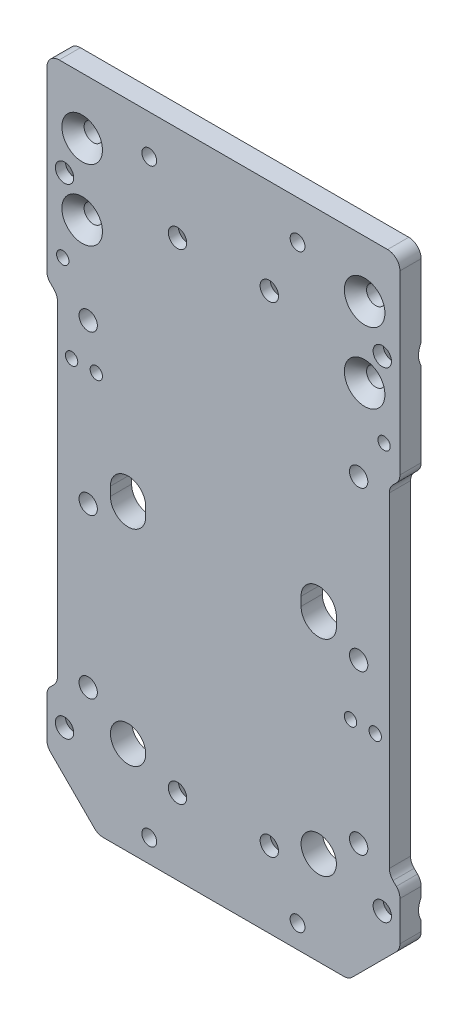
SolidWorks part; units mm, degrees
material "Acrylic (Medium-high impact)"
ref_plane "Front Plane" through (0, 0, 0) normal (0, 0, 1) x (1, 0, 0)
ref_plane "Top Plane" through (0, 0, 0) normal (0, 1, 0) x (1, 0, 0)
ref_plane "Right Plane" through (0, 0, 0) normal (1, 0, 0) x (0, 0, -1)
sketch "Sketch1" plane through (0, 0, 0) normal (0, 0, 1) x (1, 0, 0)
  line L0 (-50, 0) -> (-35.5, -14.5)
  line L1 (-50, 0) -> (50, 0)
  line L2 (-50, 0) -> (-50, 170)
  line L3 (-50, 170) -> (50, 170)
  line L4 (50, 0) -> (50, 170)
  line L5 (-35.5, -14.5) -> (35.5, -14.5)
  line L6 (35.5, -14.5) -> (50, 0)
  line L7 (0, 0) -> (0, 178.5984) construction
  point P4 (0, 0)
  point P8 (0, -14.5)
  dimension "D1" = 100
  dimension "D2" = 170
  dimension "D3" = 14.5
  dimension "D4" = 71
  dimension "D5" = 184.5
extrude "Body" add sketch "Sketch1" along normal mid plane 6 contours L1 L4 L3 L2 | L5 L6 L1 L0 | L1 L7 L3 L2 region at (0, -6.8402, 0) region at (-25, 85, 0) region at (25, 85, 0)
sketch "Sketch6" plane through (0, 0, 3) normal (0, 0, 1) x (1, 0, 0)
  line L0 (-50, 115) -> (-47, 112)
  line L1 (0, 0) -> (0, 25.1631) construction
  line L2 (-47, 112) -> (-47, 17)
  line L3 (-47, 17) -> (-50, 14)
  line L4 (50, 115) -> (47, 112)
  line L5 (-35.5, -14.5) -> (35.5, -14.5) construction
  line L6 (47, 112) -> (47, 17)
  line L7 (47, 17) -> (50, 14)
  line L8 (-50, 115) -> (-50, 14)
  line L9 (50, 115) -> (50, 14)
  line L12 (-50, 0) -> (-50, 170) construction
  line L13 (50, 0) -> (50, 170) construction
  dimension "D1" = 94
  dimension "D2" = 28.5
  dimension "D3" = 45
  dimension "D4" = 129.5
extrude "ReduceSomeWidth" cut sketch "Sketch6" against normal through all
sketch "screwHeadHoleCarriageY" plane through (0, 0, -3) normal (0, 0, -1) x (-1, 0, 0)
  line L0 (0, 0) -> (0, 34.2129) construction
  line L1 (35.5, -14.5) -> (-35.5, -14.5) construction
  line L2 (-27, 70.2) -> (-27, 72.7) construction
  line L3 (-32, 70.2) -> (-32, 72.7)
  line L4 (-22, 70.2) -> (-22, 72.7)
  line L5 (27, 70.2) -> (27, 72.7) construction
  line L6 (22, 70.2) -> (22, 72.7)
  line L7 (32, 70.2) -> (32, 72.7)
  circle A0 centre (-27, 12) radius 5
  circle A1 centre (27, 12) radius 5
  arc A6 (-32, 70.2) -> (-22, 70.2) centre (-27, 70.2) ccw
  arc A7 (-22, 72.7) -> (-32, 72.7) centre (-27, 72.7) ccw
  arc A8 (22, 70.2) -> (32, 70.2) centre (27, 70.2) ccw
  arc A9 (32, 72.7) -> (22, 72.7) centre (27, 72.7) ccw
  point P18 (-27, 71.45)
  point P28 (27, 71.45)
  dimension "D3" = 10
  dimension "D5" = 12.5
  dimension "D1" = 54
  dimension "D2" = 26.5
  dimension "D4" = 84.7
extrude "CutForOtherScrewsHeads" cut sketch "screwHeadHoleCarriageY" against normal through all
fillet "EndMillMinimumRadius" radius 3.5 14 edges at (-50, 170, 0) (50, 170, 0) (47, 112, 0) (47, 17, 0) (-47, 17, 0) (-47, 112, 0) (-50, 14, 0) (-50, 0, 0) (-35.5, -14.5, 0) (50, 14, 0) (50, 0, 0) (35.5, -14.5, 0) (-50, 115, 0) (50, 115, 0)
hole_wizard "Ø3.5 (3.5) CableTieHoles" positions "Sketch9" profile "Sketch10" hole size "Ø3.5" standard "ANSI Metric" end condition through all
sketch "Sketch9" plane through (0, 0, -3) normal (0, 0, -1) x (-1, 0, 0)
  line L0 (-50, 116.4497) -> (-50, 166.5) construction
  line L1 (50, 116.4497) -> (50, 166.5) construction
  line L2 (34.0503, -14.5) -> (-34.0503, -14.5) construction
  point P0 (-45.5, 122)
  point P2 (45.5, 122)
  dimension "D1" = 4.5
  dimension "D2" = 4.5
  dimension "D3" = 136.5
sketch "Sketch10" plane through (45.5, 122, -3) normal (1, 0, 0) x (0, 1, 0)
  line L0 (0, 0) -> (0, 6)
  line L1 (0, 6) -> (1.75, 6)
  line L2 (1.75, 6) -> (1.75, 0)
  line L5 (1.75, 0) -> (0, 0)
  line L11 (0, -6.35) -> (0, 107.95) construction
  dimension "Thru Hole Dia." = 3.5
  dimension "Thru Hole Depth" = 6
hole_wizard "Ø4.2 (4.2) KP8 Holes1" positions "Sketch11" profile "Sketch12" hole size "Ø4.2" standard "ANSI Metric" end condition through all
sketch "Sketch11" plane through (0, 0, -3) normal (0, 0, -1) x (-1, 0, 0)
  line L0 (34.0503, -14.5) -> (-34.0503, -14.5) construction
  line L2 (0, 0) -> (0, 41.1682) construction
  point P0 (-21, 159)
  point P2 (21, 159)
  dimension "D1" = 42
  dimension "D2" = 173.5
sketch "Sketch12" plane through (21, 159, -3) normal (1, 0, 0) x (0, 1, 0)
  line L0 (0, 0) -> (0, 6)
  line L1 (0, 6) -> (2.1, 6)
  line L2 (2.1, 6) -> (2.1, 0)
  line L5 (2.1, 0) -> (0, 0)
  line L11 (0, -6.35) -> (0, 107.95) construction
  dimension "Thru Hole Dia." = 4.2
  dimension "Thru Hole Depth" = 6
hole_wizard "Ø4.2 (4.2) KP8 Holes2" positions "Sketch13" profile "Sketch14" hole size "Ø4.2" standard "ANSI Metric" end condition through all
sketch "Sketch13" plane through (0, 0, -3) normal (0, 0, -1) x (-1, 0, 0)
  line L0 (34.0503, -14.5) -> (-34.0503, -14.5) construction
  line L1 (0, 0) -> (0, 17.4832) construction
  point P0 (-21, -8)
  point P2 (21, -8)
  dimension "D1" = 42
  dimension "D2" = 6.5
sketch "Sketch14" plane through (21, -8, -3) normal (1, 0, 0) x (0, 1, 0)
  line L0 (0, 0) -> (0, 6)
  line L1 (0, 6) -> (2.1, 6)
  line L2 (2.1, 6) -> (2.1, 2.7)
  line L3 (2.1, 2.7) -> (4.8, 0)
  line L5 (4.8, 0) -> (0, 0)
  line L6 (-2.1, 2.7) -> (-4.8, 0) construction
  line L11 (0, -6.35) -> (0, 107.95) construction
  dimension "Thru Hole Dia." = 4.2
  dimension "Thru Hole Depth" = 6
  dimension "Near C'Sink Dia." = 9.6
  dimension "Near C'Sink Angle" = 90
hole_wizard "Ø5.2 (5.2) MountAngleCornerHoles" positions "Sketch15" profile "Sketch16" hole size "Ø5.2" standard "ANSI Metric" end condition through all
sketch "Sketch15" plane through (0, 0, -3) normal (0, 0, -1) x (-1, 0, 0)
  line L0 (0, 0) -> (0, 24.2214) construction
  line L2 (46.5, 170) -> (-46.5, 170) construction
  point P0 (-40, 154)
  point P2 (-40, 134)
  point P4 (40, 154)
  point P6 (40, 134)
  dimension "D1" = 80
  dimension "D2" = 20
  dimension "D3" = 16
sketch "Sketch16" plane through (40, 154, -3) normal (1, 0, 0) x (0, 1, 0)
  line L0 (0, 0) -> (0, 6)
  line L1 (0, 6) -> (5.75, 6)
  line L2 (2.6, 2.85) -> (2.6, 0)
  line L5 (2.6, 0) -> (0, 0)
  line L7 (5.75, 6) -> (2.6, 2.85)
  line L8 (-5.75, 6) -> (-2.6, 2.85) construction
  line L11 (0, -6.35) -> (0, 107.95) construction
  dimension "Thru Hole Dia." = 5.2
  dimension "Thru Hole Depth" = 6
  dimension "Far C'Sink Dia." = 11.5
  dimension "Far C'Sink Angle" = 90
hole_wizard "Ø5.2 (5.2) SK8 Mount Holes" positions "Sketch17" profile "Sketch20" hole size "Ø5.2" standard "ANSI Metric" end condition through all
sketch "Sketch17" plane through (0, 0, -3) normal (0, 0, -1) x (-1, 0, 0)
  line L0 (0, 0) -> (0, 35.1955) construction
  line L1 (34.0503, -14.5) -> (-34.0503, -14.5) construction
  point P0 (-45, 143.1)
  point P2 (-13, 143.1)
  point P4 (13, 143.1)
  point P6 (45, 143.1)
  point P8 (-45, 7)
  point P10 (-13, 7)
  point P12 (13, 7)
  point P14 (45, 7)
  point P23 (0, 0)
  point P24 (-9.1751, 131.7209)
  point P25 (0, 0)
  point P26 (0, 0)
  point P27 (0, 0)
  point P28 (0, 0)
  point P29 (0, 0)
  dimension "D1" = 32
  dimension "D2" = 26
  dimension "D3" = 32
  dimension "D4" = 21.5
  dimension "D5" = 157.6
sketch "Sketch20" plane through (45, 143.1, -3) normal (1, 0, 0) x (0, 1, 0)
  line L0 (0, 0) -> (0, 6)
  line L1 (0, 6) -> (2.6, 6)
  line L2 (2.6, 6) -> (2.6, 3.15)
  line L3 (2.6, 3.15) -> (5.75, 0)
  line L5 (5.75, 0) -> (0, 0)
  line L6 (-2.6, 3.15) -> (-5.75, 0) construction
  line L11 (0, -6.35) -> (0, 107.95) construction
  dimension "Thru Hole Dia." = 5.2
  dimension "Thru Hole Depth" = 6
  dimension "Near C'Sink Dia." = 11.5
  dimension "Near C'Sink Angle" = 90
hole_wizard "Ø3.5 (3.5) EndSensorsHoles" positions "Sketch21" profile "Sketch22" hole size "Ø3.5" standard "ANSI Metric" end condition through all
sketch "Sketch21" plane through (0, 0, -3) normal (0, 0, -1) x (-1, 0, 0)
  line L2 (34.0503, -14.5) -> (-34.0503, -14.5) construction
  point P0 (-43, 49.5)
  point P2 (-36, 49.5)
  point P4 (36, 98.5)
  point P6 (43, 98.5)
  point P9 (0, 0)
  point P10 (0, 0)
  dimension "D1" = 7
  dimension "D2" = 7
  dimension "D3" = 72
  dimension "D4" = 64
  dimension "D5" = 113
sketch "Sketch22" plane through (43, 49.5, -3) normal (1, 0, 0) x (0, 1, 0)
  line L0 (0, 0) -> (0, 6)
  line L1 (0, 6) -> (1.75, 6)
  line L2 (1.75, 6) -> (1.75, 1.5)
  line L3 (1.75, 1.5) -> (3.25, 0)
  line L5 (3.25, 0) -> (0, 0)
  line L6 (-1.75, 1.5) -> (-3.25, 0) construction
  line L11 (0, -6.35) -> (0, 107.95) construction
  dimension "Thru Hole Dia." = 3.5
  dimension "Thru Hole Depth" = 6
  dimension "Near C'Sink Dia." = 6.5
  dimension "Near C'Sink Angle" = 90
hole_wizard "Ø5.2 (5.2) MountToBaseHoles" positions "Sketch23" profile "Sketch24" hole size "Ø5.2" standard "ANSI Metric" end condition through all
sketch "Sketch23" plane through (0, 0, 3) normal (0, 0, 1) x (1, 0, 0)
  line L0 (0, 0) -> (0, 21.7136) construction
  line L3 (-34.0503, -14.5) -> (34.0503, -14.5) construction
  point P0 (-38.3, 110.2)
  point P2 (-38.3, 65.2)
  point P4 (-38.3, 20.2)
  point P6 (38.3, 20.2)
  point P8 (38.3, 65.2)
  point P10 (38.3, 110.2)
  point P23 (0, 0)
  point P26 (0, 0)
  dimension "D1" = 76.6
  dimension "D2" = 34.7
  dimension "D3" = 124.7
  dimension "D4" = 79.7
sketch "Sketch24" plane through (-38.3, 110.2, 3) normal (1, 0, 0) x (0, -1, 0)
  line L0 (0, 0) -> (0, 6)
  line L1 (0, 6) -> (2.6, 6)
  line L2 (2.6, 6) -> (2.6, 0)
  line L5 (2.6, 0) -> (0, 0)
  line L11 (0, -6.35) -> (0, 107.95) construction
  dimension "Thru Hole Dia." = 5.2
  dimension "Thru Hole Depth" = 6
